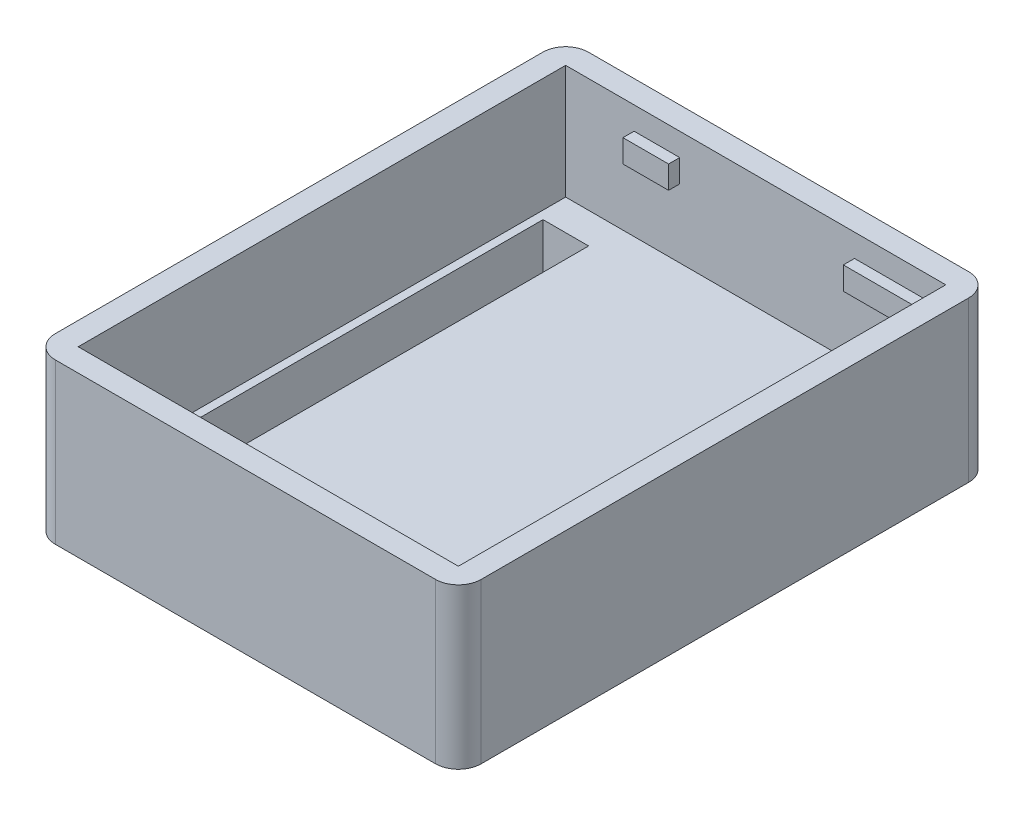
SolidWorks part; units mm, degrees
ref_plane "Plan de face" through (0, 0, 0) normal (0, 0, 1) x (1, 0, 0)
ref_plane "Plan de dessus" through (0, 0, 0) normal (0, 1, 0) x (1, 0, 0)
ref_plane "Plan de droite" through (0, 0, 0) normal (1, 0, 0) x (0, 0, -1)
sketch "Esquisse1" plane through (0, 0, 0) normal (0, 1, 0) x (1, 0, 0)
  line L1 (1, 0) -> (17.6601, 0)
  line L2 (0, 1) -> (0, 22.3619)
  line L3 (1, 23.3619) -> (17.6601, 23.3619)
  line L4 (18.6601, 1) -> (18.6601, 22.3619)
  arc A0 (17.6601, 0) -> (18.6601, 1) centre (17.6601, 1) ccw
  arc A1 (17.6601, 23.3619) -> (18.6601, 22.3619) centre (17.6601, 22.3619) cw
  arc A2 (0, 22.3619) -> (1, 23.3619) centre (1, 22.3619) cw
  arc A3 (1, 0) -> (0, 1) centre (1, 1) cw
  point P7 (18.6601, 0)
  point P12 (0, 23.3619)
  point P15 (0, 0)
  dimension "D3" = 1
  dimension "D1" = 23.3619
  dimension "D2" = 18.6601
extrude "Boss.-Extru.1" add sketch "Esquisse1" along normal blind 7 contours L1 A0 L4 A1 L3 A2 L2 A3
sketch "Esquisse2" plane through (0, 7, 0) normal (0, 1, 0) x (1, 0, 0)
  line L8 (1, 1) -> (17.6601, 1)
  line L9 (17.6601, 1) -> (17.6601, 22.3619)
  line L10 (17.6601, 22.3619) -> (1, 22.3619)
  line L11 (1, 22.3619) -> (1, 1)
  line L12 (1, 1) -> (17.6601, 1)
  line L13 (17.6601, 1) -> (17.6601, 22.3619)
  line L14 (17.6601, 22.3619) -> (1, 22.3619)
  line L15 (1, 22.3619) -> (1, 1)
  dimension "D1" = 1
extrude "Enlèv. mat.-Extru.1" cut sketch "Esquisse2" against normal blind 5
sketch "Esquisse5" plane through (0, 2, 0) normal (0, 1, 0) x (1, 0, 0)
  line L0 (1, 1) -> (17.6601, 1) construction
  line L1 (3.36, 21.01) -> (1.36, 21.01)
  line L2 (3.36, 21.01) -> (3.36, 1.25)
  line L3 (3.36, 1.25) -> (1.36, 1.25)
  line L4 (1.36, 21.01) -> (1.36, 1.25)
  line L5 (1, 22.3619) -> (1, 1) construction
  dimension "D1" = 19.76
  dimension "D2" = 2
  dimension "D3" = 0.25
  dimension "D4" = 0.36
extrude "Enlèv. mat.-Extru.3" cut sketch "Esquisse5" against normal through all
sketch "Esquisse6" plane through (0, 0, -22.3619) normal (0, 0, 1) x (1, 0, 0)
  line L0 (17.6601, 2) -> (17.6601, 7) construction
  line L1 (16.6601, 5) -> (13.6601, 5)
  line L2 (16.6601, 5) -> (16.6601, 6)
  line L3 (16.6601, 6) -> (13.6601, 6)
  line L4 (13.6601, 5) -> (13.6601, 6)
  line L5 (17.6601, 2) -> (1, 2) construction
  dimension "D1" = 3
  dimension "D2" = 1
  dimension "D3" = 1
  dimension "D4" = 3
extrude "Boss.-Extru.2" add sketch "Esquisse6" along normal blind 0.489
sketch "Esquisse7" plane through (17.6601, 0, 0) normal (-1, 0, 0) x (0, 0, 1)
  line L0 (-22.3619, 2) -> (-22.3619, 7) construction
  line L1 (-21.3618, 5) -> (-18.3619, 5)
  line L2 (-21.3618, 5) -> (-21.3618, 6)
  line L3 (-21.3618, 6) -> (-18.3619, 6)
  line L4 (-18.3619, 5) -> (-18.3619, 6)
  line L5 (-1, 2) -> (-22.3619, 2) construction
  dimension "D1" = 3
  dimension "D2" = 1
  dimension "D3" = 1
  dimension "D4" = 3
extrude "Boss.-Extru.3" add sketch "Esquisse7" along normal blind 0.489
sketch "Esquisse8" plane through (0, 0, -1) normal (0, 0, -1) x (-1, 0, 0)
  line L0 (-17.6601, 2) -> (-17.6601, 7) construction
  line L1 (-16.6601, 6) -> (-13.6601, 6)
  line L2 (-16.6601, 6) -> (-16.6601, 5)
  line L3 (-16.6601, 5) -> (-13.6601, 5)
  line L4 (-13.6601, 6) -> (-13.6601, 5)
  line L5 (-1, 2) -> (-17.6601, 2) construction
  dimension "D1" = 3
  dimension "D2" = 1
  dimension "D3" = 1
  dimension "D4" = 3
extrude "Boss.-Extru.4" add sketch "Esquisse8" along normal blind 0.489
sketch "Esquisse9" plane through (17.6601, 0, 0) normal (-1, 0, 0) x (0, 0, 1)
  line L0 (-1, 2) -> (-22.3619, 2) construction
  line L1 (-2, 6) -> (-5, 6)
  line L2 (-2, 6) -> (-2, 5)
  line L3 (-2, 5) -> (-5, 5)
  line L4 (-5, 6) -> (-5, 5)
  line L5 (-1, 2) -> (-1, 7) construction
  dimension "D1" = 3
  dimension "D2" = 1
  dimension "D3" = 3
  dimension "D4" = 1
extrude "Boss.-Extru.5" add sketch "Esquisse9" along normal blind 0.489
sketch "Esquisse10" plane through (0, 0, -22.3619) normal (0, 0, 1) x (1, 0, 0)
  line L0 (1, 2) -> (1, 7) construction
  line L1 (4, 5) -> (6, 5)
  line L2 (4, 5) -> (4, 6)
  line L3 (4, 6) -> (6, 6)
  line L4 (6, 5) -> (6, 6)
  line L5 (17.6601, 2) -> (1, 2) construction
  dimension "D1" = 2
  dimension "D2" = 1
  dimension "D3" = 3
  dimension "D4" = 3
extrude "Boss.-Extru.6" add sketch "Esquisse10" along normal blind 0.489
sketch "Esquisse11" plane through (0, 0, -1) normal (0, 0, -1) x (-1, 0, 0)
  line L0 (-1, 2) -> (-17.6601, 2) construction
  line L1 (-4, 6) -> (-6, 6)
  line L2 (-4, 6) -> (-4, 5)
  line L3 (-4, 5) -> (-6, 5)
  line L4 (-6, 6) -> (-6, 5)
  line L5 (-1, 2) -> (-1, 7) construction
  dimension "D1" = 2
  dimension "D2" = 1
  dimension "D3" = 3
  dimension "D4" = 3
extrude "Boss.-Extru.7" add sketch "Esquisse11" along normal blind 0.489
